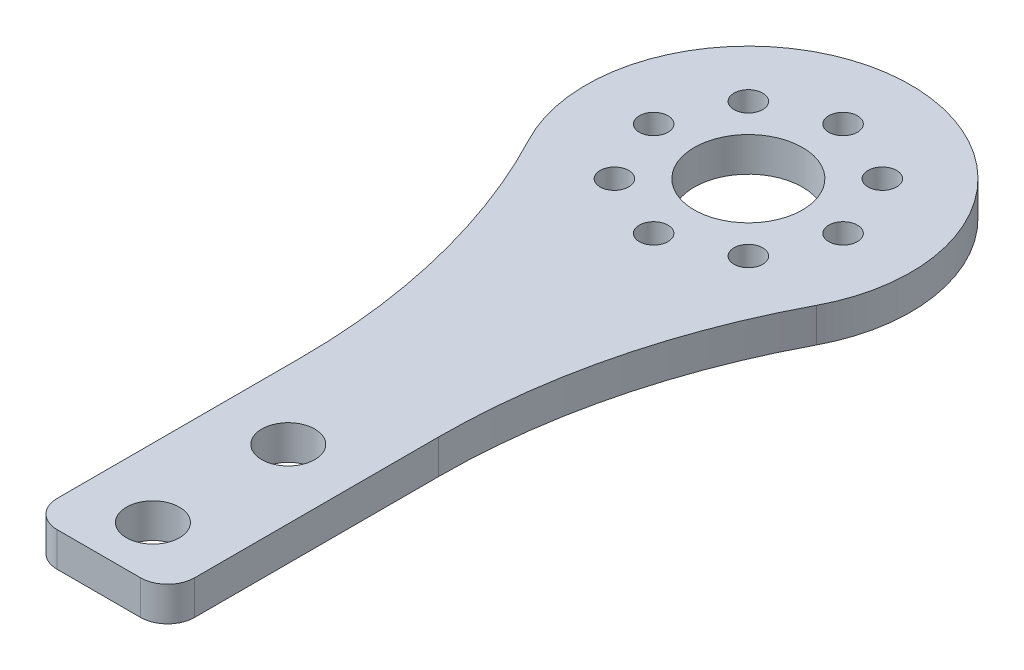
SolidWorks part; units mm, degrees
material "1060 Alloy"
ref_plane "Front Plane" through (0, 0, 0) normal (0, 0, 1) x (1, 0, 0)
ref_plane "Top Plane" through (0, 0, 0) normal (0, 1, 0) x (1, 0, 0)
ref_plane "Right Plane" through (0, 0, 0) normal (1, 0, 0) x (0, 0, -1)
sketch "Sketch1" plane through (0, 0, 0) normal (0, 1, 0) x (1, 0, 0)
  line L0 (-12.7, -120) -> (12.7, -120)
  line L1 (12.7, -120) -> (12.7, -27.1792)
  line L2 (-12.7, -120) -> (-12.7, -27.1792)
  line L3 (0, -120) -> (0, -85) construction
  arc A0 (12.7, -27.1792) -> (-12.7, -27.1792) centre (0, 0) ccw
  point P1 (0, -85)
  point P5 (0, -120)
  point P7 (0, -110)
  dimension "D2" = 60
  dimension "D1" = 25.4
  dimension "D3" = 85
  dimension "D4" = 25
  dimension "D5" = 10
extrude "Boss-Extrude1" add sketch "Sketch1" along normal blind 6.35 contours A0 L2 L0 L1
sketch "Sketch2" plane through (0, 0, 0) normal (0, -1, 0) x (1, 0, 0)
  circle A0 centre (0, 0) radius 17.5 construction
  point P3 (17.5, 0)
  point P6 (12.3744, -12.3744)
  point P7 (0, -17.5)
  point P8 (-12.3744, -12.3744)
  point P9 (-17.5, 0)
  point P10 (-12.3744, 12.3744)
  point P11 (0, 17.5)
  point P12 (12.3744, 12.3744)
  point P13 (0, 0)
  dimension "D2" = 35
  dimension "D1" = 8
hole_wizard "M5 Clearance Hole1" positions "Sketch3" profile "Sketch4" hole size "M5" standard "ANSI Metric" end condition through all
sketch "Sketch3" plane through (0, 0, 0) normal (0, -1, 0) x (-1, 0, 0)
  point P0 (0, 17.5)
  point P3 (12.3744, 12.3744)
  point P6 (17.5, 0)
  point P9 (12.3744, -12.3744)
  point P12 (0, -17.5)
  point P15 (-12.3744, -12.3744)
  point P18 (-17.5, 0)
  point P21 (-12.3744, 12.3744)
sketch "Sketch4" plane through (0, 0, -17.5) normal (1, 0, 0) x (0, 0, -1)
  line L0 (0, 0) -> (0, 6.35)
  line L1 (0, 6.35) -> (2.65, 6.35)
  line L2 (2.65, 6.35) -> (2.65, 0)
  line L5 (2.65, 0) -> (0, 0)
  line L11 (0, -6.35) -> (0, 107.95) construction
  dimension "Thru Hole Dia." = 5.3
  dimension "Thru Hole Depth" = 6.35
sketch "Sketch5" plane through (0, 0, 0) normal (0, -1, 0) x (1, 0, 0)
  circle A0 centre (0, 0) radius 10
  dimension "D1" = 20
extrude "Cut-Extrude1" cut sketch "Sketch5" against normal through all
hole_wizard "3/8 Clearance Hole1" positions "Sketch9" profile "Sketch11" hole size "3/8" standard "ANSI Inch" end condition through all
sketch "Sketch9" plane through (0, 0, 0) normal (0, -1, 0) x (-1, 0, 0)
  point P0 (0, -85)
  point P3 (0, -110)
sketch "Sketch11" plane through (0, 0, 85) normal (1, 0, 0) x (0, 0, -1)
  line L0 (0, 0) -> (0, 6.35)
  line L1 (0, 6.35) -> (4.9022, 6.35)
  line L2 (4.9022, 6.35) -> (4.9022, 0)
  line L5 (4.9022, 0) -> (0, 0)
  line L11 (0, -6.35) -> (0, 107.95) construction
  dimension "Thru Hole Dia." = 9.8044
  dimension "Thru Hole Depth" = 6.35
fillet "Fillet1" radius 120 2 edges at (-12.7, 3.175, 27.1792) (12.7, 3.175, 27.1792)
fillet "Fillet2" radius 5 2 edges at (12.7, 3.175, 120) (-12.7, 3.175, 120)
ref_axis "Axis1" through (0, -0.3175, 0) along (0, 1, 0)
